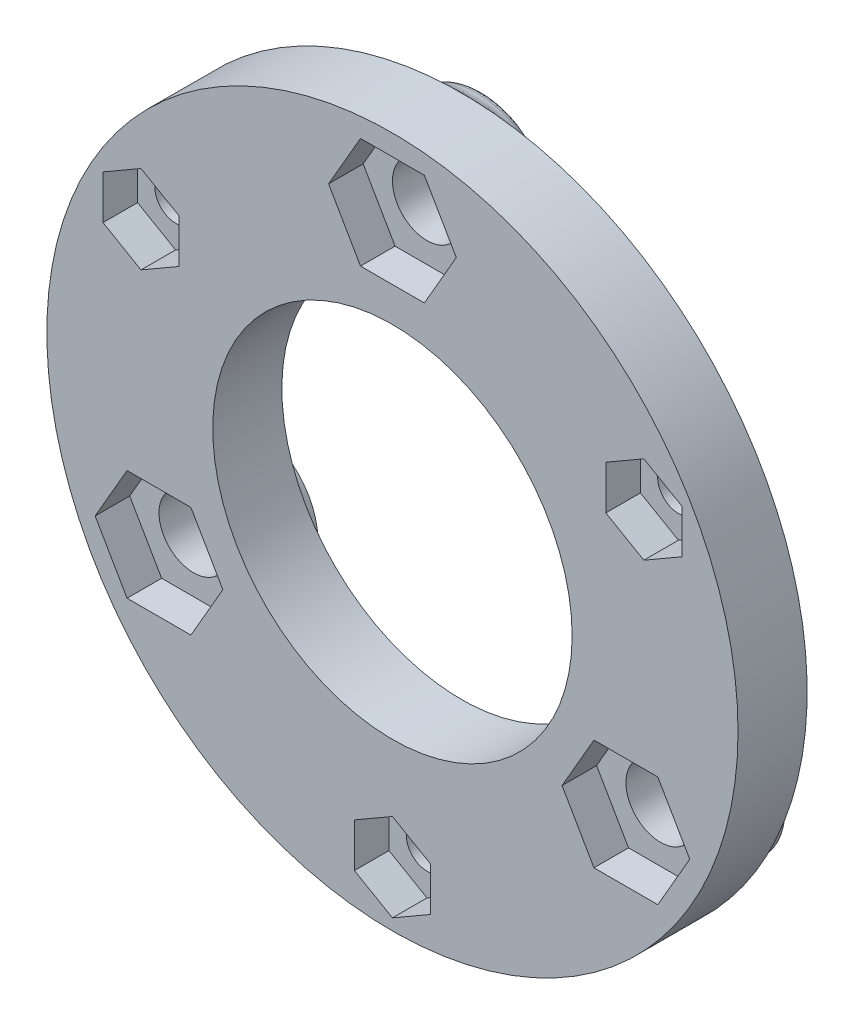
SolidWorks part; units mm, degrees
material "ABS"
ref_plane "Front Plane" through (0, 0, 0) normal (0, 0, 1) x (1, 0, 0)
ref_plane "Top Plane" through (0, 0, 0) normal (0, 1, 0) x (1, 0, 0)
ref_plane "Right Plane" through (0, 0, 0) normal (1, 0, 0) x (0, 0, -1)
sketch "Sketch2" plane through (0, 0, 0) normal (0, 0, 1) x (1, 0, 0)
  line L0 (0, 19.5) -> (0, 0) construction
  line L1 (0, 0) -> (18.1865, 10.5) construction
  circle A0 centre (0, 0) radius 25
  circle A1 centre (0, 0) radius 13
  circle A2 centre (0, 0) radius 19.5 construction
  circle A3 centre (0, 19.5) radius 2.5
  circle A4 centre (0, 0) radius 21 construction
  circle A5 centre (16.8875, -9.75) radius 2.5
  circle A8 centre (18.1865, 10.5) radius 1.5
  circle A9 centre (0, -21) radius 1.5
  circle A11 centre (0, 0) radius 8.25 construction
  circle A14 centre (0, 19.5) radius 5 construction
  circle A15 centre (0, 0) radius 14.5 construction
  circle A16 centre (-16.8875, -9.75) radius 2.5
  circle A19 centre (-18.1865, 10.5) radius 1.5
  point P17 (0, 0)
  point P24 (0, 0)
  dimension "D1" = 50
  dimension "D2" = 39
  dimension "D4" = 5
  dimension "D7" = 3
  dimension "D3" = 16.5
  dimension "D10" = 10
  dimension "D5" = 4
  dimension "D9" = 1.5
  dimension "D11" = 60
  dimension "D6" = 3
  dimension "D8" = 3
extrude "Boss-Extrude1" add sketch "Sketch2" along normal blind 5
sketch "Sketch3" plane through (0, 0, 5) normal (0, 0, 1) x (1, 0, 0)
  line L0 (0, 19.5) -> (0, 0) construction
  line L13 (-4.6188, 19.5) -> (-2.3094, 15.5)
  line L14 (-2.3094, 15.5) -> (2.3094, 15.5)
  line L15 (2.3094, 15.5) -> (4.6188, 19.5)
  line L16 (4.6188, 19.5) -> (2.3094, 23.5)
  line L17 (2.3094, 23.5) -> (-2.3094, 23.5)
  line L18 (-2.3094, 23.5) -> (-4.6188, 19.5)
  line L20 (18.1865, 7.3246) -> (20.9365, 8.9123)
  line L21 (20.9365, 8.9123) -> (20.9365, 12.0877)
  line L22 (20.9365, 12.0877) -> (18.1865, 13.6754)
  line L23 (18.1865, 13.6754) -> (15.4365, 12.0877)
  line L24 (15.4365, 12.0877) -> (15.4365, 8.9123)
  line L25 (15.4365, 8.9123) -> (18.1865, 7.3246)
  circle A0 centre (0, 19.5) radius 4 construction
  circle A1 centre (18.1865, 10.5) radius 2.75 construction
  dimension "D1" = 8
  dimension "D2" = 5.5
extrude "Cut-Extrude1" cut sketch "Sketch3" against normal blind 2.5
pattern_circular "CirPattern1" count 3 over 360 about axis through (0, 0, 5) along (0, 0, -1) of "Cut-Extrude1" reverse direction yes
sketch "Sketch4" plane through (0, 0, 0) normal (0, 0, -1) x (-1, 0, 0)
  circle A0 centre (0, 19.5) radius 4
  circle A1 centre (0, 19.5) radius 5
  dimension "D1" = 8
extrude "Boss-Extrude2" add sketch "Sketch4" along normal blind 1.5
fillet "Fillet1" radius 1.5 1 edges at (5, 19.5, 0)
fillet "Fillet2" radius 0.5 2 edges at (0, 24.5, -1.5) (0, 14.5, -1.5)
chamfer "Chamfer1" distance 0.25 angle 45 1 edges at (-4, 19.5, -1.5)
pattern_circular "CirPattern2" count 3 over 360 about axis through (0, 0, 5) along (0, 0, -1) of "Fillet1", "Boss-Extrude2", "Chamfer1" reverse direction yes
equation "\"Nr\" = 123"
equation "\"module\" = 0.5"
equation "\"pressure_angle\" = 20.0"
equation "\"h_a\" = 0.5"
equation "\"h_f\" = 0.625"
equation "\"clr_tip_root\" = 0.125"
equation "\"dp_r\" = 61.5"
equation "\"db_r\" = 57.79109617833337"
equation "\"fw_r\" = 8.0"
equation "\"alpha_r\" = 0.8539582918412414"
equation "\"beta_r\" = 3.171331217828824"
equation "\"bearing_ID\" = 50"
equation "\"bearing_OD\" = 65"
equation "\"bearing_height\" = 7"
equation "\"clearance_planet\" = 1.5"
equation "\"case_dist\" = 6.5"
equation "\"Motor_case_OD_max\" = 96.5"
equation "\"case_mounting_PCD\" = 89.0"
equation "\"bearing mount thickness\" = 8"
equation "\"case_mounting_hole_dia\" = 3"
equation "\"output_mounting_PCD\" = 73"
equation "\"output_mounting_hole_dia\" = 4"
equation "\"clearance_case_mount_holes_shell_thickness\" = 1"
equation "\"motor_case_OD_base\" = 87.0"
equation "\"sec_carrier_thickness\" = 5"
equation "\"sun_coupler_hub_thickness\" = 4"
equation "\"clearance_sun_coupler_sec_carrier\" = 1.5"
equation "\"clearance_motor_and_case\" = 5"
equation "\"motor_OD\" = 72"
equation "\"Motor_case_thickness\" = 2.5"
equation "\"Motor_case_ID\" = 82"
equation "\"case_mounting_hole_shift\" = 1.0"
equation "\"output_mounting_nut_wrench_size\" = 7"
equation "\"output_mounting_nut_thickness\" = 3.2"
equation "\"case_mounting_hole_allen_socket_dia\" = 5.5"
equation "\"output_mounting_nut_depth\" = 3"
equation "\"case_mounting_bolt_depth\" = 4.5"
equation "\"Ns\" = 33"
equation "\"Np\" = 45"
equation "\"ring_radial_thickness\" = 5"
equation "\"ring_OD\" = 71.5"
equation "\"ring_to_chamfer_clearance\" = 2"
equation "\"Motor_case_OD_base_to_chamfer\" = 5"
equation "\"pattern_offset_from_motor_case_OD_base\" = 3"
equation "\"pattern_bulge_dia\" = 3"
equation "\"pattern_num_bulge\" = 18"
equation "\"pattern_depth\" = 2"
equation "\"motor_height\" = 27"
equation "\"case_mounting_wrench_size\" = 5.5"
equation "\"case_mounting_nut_clearance\" = 2"
equation "\"base_plate_thickness\" = 4"
equation "\"case_mounting_nut_thickness\" = 2.4"
equation "\"case_mounting_surface_height\" = 4"
equation "\"motor_mount_hole_PCD\" = 32"
equation "\"motor_mount_hole_dia\" = 4"
equation "\"motor_mount_hole_num\" = 4"
equation "\"central_hole_offset_from_motor_mount_PCD\" = 5"
equation "\"wire_slot_dist_from_center\" = 30"
equation "\"wire_slot_length\" = 10"
equation "\"wire_slot_radius\" = 2.5"
equation "\"driver_upper_holes_dist_from_center\" = 23"
equation "\"driver_lower_holes_dist_from_center\" = 15"
equation "\"driver_side_holes_dist_from_center\" = 20"
equation "\"driver_mount_holes_dia\" = 2.5"
equation "\"driver_mount_inserts_OD\" = 3.5"
equation "\"driver_mount_thickness\" = 1.5"
equation "\"driver_mount_height\" = 4"
equation "\"air_flow_hole_offset\" = 3"
equation "\"num_planet\" = 3"
equation "\"planet_pin_bolt_dia\" = 5"
equation "\"planet_pin_socket_head_dia\" = 8.5"
equation "\"carrier_PCD\" = 39.0"
equation "\"D1@Sketch2\"=\"bearing_ID\""
equation "\"D2@Sketch2\"=\"carrier_PCD\""
equation "\"D4@Sketch2\"=\"planet_pin_bolt_dia\""
equation "\"D6@Sketch2\"=\"num_planet\""
equation "\"D8@Sketch2\"=\"num_planet\""
equation "\"D1@CirPattern1\"=\"num_planet\""
equation "\"planet_shaft_dia\" = 8"
equation "\"fw_p\" = 8.0"
equation "\"planet_shaft_step_offset\" = 1"
equation "\"carrier_trapezoidal_support_sun_offset\" = 5"
equation "\"carrier_trapezoidal_support_hole_PCD_offset_bearing_ID\" = 4"
equation "\"carrier_trapezoidal_support_hole_dia\" = 3"
equation "\"carrier_trapezoidal_support_hole_socket_head_dia\" = 5.5"
equation "\"carrier_bearing_step_width\" = 1.5"
equation "\"standard_clearance_1_5mm\" = 1.5"
equation "\"standard_fillet_1_5mm\" = 1.5"
equation "\"sun_shaft_bearing_OD\" = 16"
equation "\"sun_shaft_bearing_width\" = 5"
equation "\"standard_bearing_insertion_chamfer\" = 0.5"
equation "\"D7@Sketch2\"=\"carrier_trapezoidal_support_hole_dia\""
equation "\"D5@Sketch2\"=\"carrier_trapezoidal_support_hole_PCD_offset_bearing_ID\""
equation "\"D3@Sketch2\"=\"Ns\"*\"module\""
equation "\"carrier_trapezoidal_support_hole_wrench_size\" = 5.5"
equation "\"planet_pin_bolt_wrench_size\" = 8"
equation "\"D1@Boss-Extrude1\"=\"sec_carrier_thickness\""
equation "\"D1@Cut-Extrude1\"=\"sec_carrier_thickness\"/2"
equation "\"D1@Sketch4\"=\"planet_shaft_dia\""
equation "\"D2@Sketch4\"=\"planet_shaft_step_offset\""
equation "\"D1@Boss-Extrude2\"=\"clearance_planet\""
equation "\"D1@Fillet1\"=\"standard_fillet_1_5mm\""
equation "\"D1@Chamfer1\"=\"standard_bearing_insertion_chamfer\"/2"
equation "\"D1@Fillet2\"=\"standard_fillet_1_5mm\"/3"
equation "\"D1@CirPattern2\"=\"num_planet\""
equation "\"D10@Sketch2\"=\"planet_shaft_dia\"+\"planet_shaft_step_offset\"*2"
equation "\"D9@Sketch2\"=\"standard_clearance_1_5mm\""
equation "\"D1@Sketch3\"=\"planet_pin_bolt_wrench_size\""
equation "\"D11@Sketch2\"=180/\"num_planet\""
equation "\"D2@Sketch3\"=\"carrier_trapezoidal_support_hole_wrench_size\""
equation "\"pressure angle\" = 20.0"
equation "\"motor_output_hole_PCD\" = 22"
equation "\"motor_output_hole_dia\" = 3"
equation "\"motor_output_hole_num\" = 4"
equation "\"h_b\" = 0.625"
equation "\"dp_s\" = 16.5"
equation "\"db_s\" = 15.50492824296749"
equation "\"fw_s_calc\" = 1.2595130854287364"
equation "\"alpha_s\" = 0.8539582918412449"
equation "\"beta_s\" = 3.7466288708629643"
equation "\"dp_p\" = 22.5"
equation "\"db_p\" = 21.14308396768294"
equation "\"alpha_p\" = 0.8539582918412307"
equation "\"beta_p\" = 2.2920834163175385"
equation "\"planet_bearing_OD\" = 12"
equation "\"planet_bearing_width\" = 3.5"
equation "\"planet_bore\" = 10"
equation "\"sun_shaft_bearing_ID\" = 8"
equation "\"sun_hub_dia\" = 31.0"
equation "\"sun_central_bolt_dia\" = 5"
equation "\"sun_central_bolt_socket_head_dia\" = 8.5"
equation "\"fw_s_used\" = 16.0"
equation "\"motor_output_hole_CSK_OD\" = 6"
equation "\"motor_output_hole_CSK_head_height\" = 1.5"
equation "\"bearing_retainer_thickness\" = 2"
